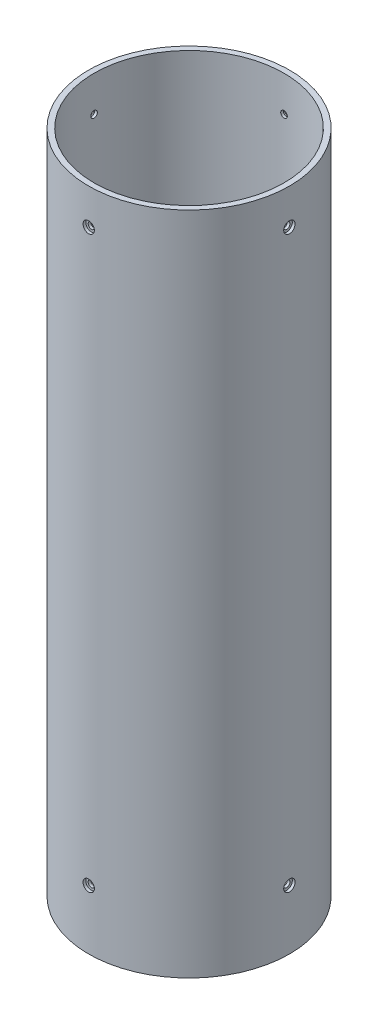
SolidWorks part; units mm, degrees
material "Hexcel AS4C (3000 Filaments)"
ref_plane "Front Plane" through (0, 0, 0) normal (0, 0, 1) x (1, 0, 0)
ref_plane "Top Plane" through (0, 0, 0) normal (0, 1, 0) x (1, 0, 0)
ref_plane "Right Plane" through (0, 0, 0) normal (1, 0, 0) x (0, 0, -1)
sketch "Sketch1" plane through (0, 0, 0) normal (0, 1, 0) x (1, 0, 0)
  circle A0 centre (0, 0) radius 50.8
  dimension "D1" = 101.6
extrude "Body Extrusion" add sketch "Sketch1" along normal blind 355.6 thin thin type one direction wall 2.921
ref_plane "Plane1" through (0, 0, 53.721) normal (0, 0, 1) x (1, 0, 0)
sketch "Sketch2" plane through (0, 0, 53.721) normal (0, 0, 1) x (1, 0, 0)
  line L0 (0, 355.6) -> (0, 0) construction
  line L1 (53.721, 355.6) -> (-53.721, 355.6) construction
  line L3 (50.8, 355.6) -> (-50.8, 355.6) construction
  circle A0 centre (0, 336.55) radius 1.7526
  dimension "D1" = 3.5052
  dimension "D2" = 19.05
extrude "Upper Bulkhead Holes" cut sketch "Sketch2" against normal up to next
pattern_circular "Upper Bulkhead Hole Pattern" count 4 over 360 about axis through (0, 355.6, 0) along (0, -1, 0) of "Upper Bulkhead Holes"
sketch "Sketch3" plane through (0, 0, 53.721) normal (0, 0, 1) x (1, 0, 0)
  line L0 (0, 355.6) -> (0, 0) construction
  line L1 (53.721, 355.6) -> (-53.721, 355.6) construction
  line L2 (50.8, 355.6) -> (-50.8, 355.6) construction
  circle A0 centre (0, 31.75) radius 1.7526
  dimension "D1" = 3.5052
  dimension "D2" = 31.75
  dimension "D3" = 323.85
extrude "Lower Bulkhead Holes" cut sketch "Sketch3" against normal up to next
pattern_circular "Lower Bulkhead Hole Pattern" count 4 over 360 about axis through (0, 355.6, 0) along (0, -1, 0) of "Lower Bulkhead Holes" reverse direction yes
sketch "Sketch4" plane through (0, 0, 53.721) normal (0, 0, 1) x (1, 0, 0)
  line L0 (0, 355.6) -> (0, 0) construction
  line L1 (50.8, 355.6) -> (-50.8, 355.6) construction
  line L2 (-50.8, 0) -> (50.8, 0) construction
  circle A0 centre (0, 336.55) radius 3.0226
  circle A1 centre (0, 31.75) radius 3.0226
  circle A2 centre (0, 31.75) radius 1.7526 construction
  circle A3 centre (0, 336.55) radius 1.7526 construction
  dimension "D1" = 1.27
  dimension "D2" = 1.27
extrude "Countersink" cut sketch "Sketch4" against normal blind 1.524
pattern_circular "Countersink Pattern" count 4 over 360 about axis through (0, 355.6, 0) along (0, -1, 0) of "Countersink"
equation "\"D2@Sketch4\"=\"D1@Sketch4\""
